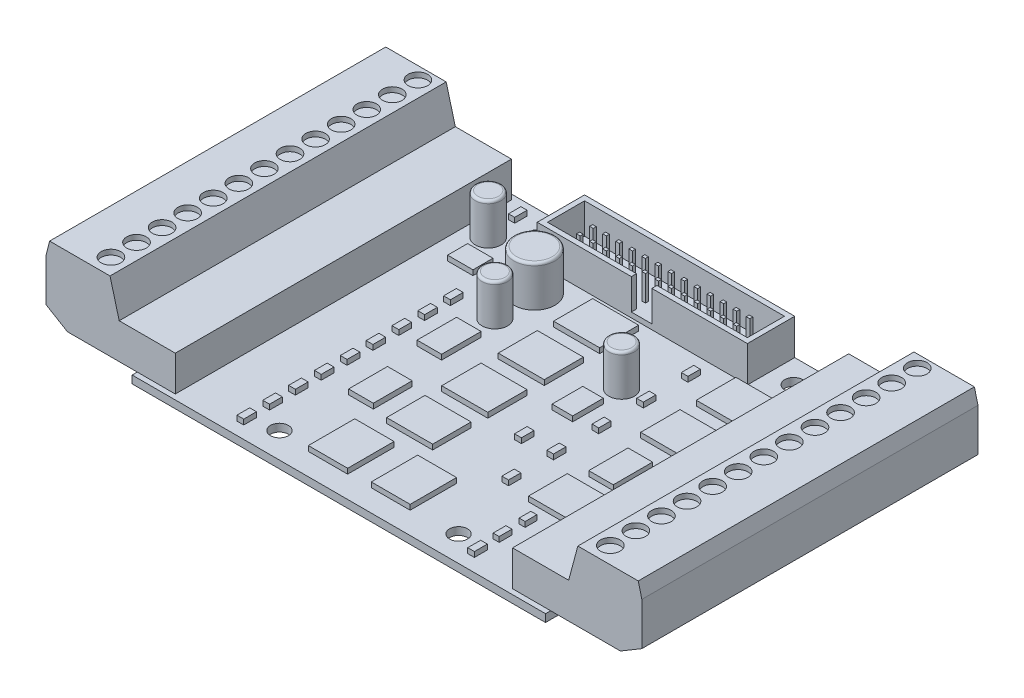
SolidWorks part; units mm, degrees
ref_plane "Front Plane" through (0, 0, 0) normal (0, 0, 1) x (1, 0, 0)
ref_plane "Top Plane" through (0, 0, 0) normal (0, 1, 0) x (1, 0, 0)
ref_plane "Right Plane" through (0, 0, 0) normal (1, 0, 0) x (0, 0, -1)
sketch "Sketch1" plane through (0, 0, 0) normal (0, 1, 0) x (1, 0, 0)
  line L0 (91.1211, 240.7605) -> (689.1211, 240.7605) construction
  line L1 (55.2, -33.85) -> (-55.2, -33.85)
  line L2 (55.2, -33.85) -> (55.2, 33.85)
  line L3 (55.2, 33.85) -> (-55.2, 33.85)
  line L4 (-55.2, -33.85) -> (-55.2, 33.85)
  line L5 (0, 33.85) -> (0, -33.85) construction
  line L6 (55.2, 0) -> (-55.2, 0) construction
  point P0 (0, 0)
  dimension "D1" = 110.4
  dimension "D2" = 67.7
sketch "Sketch3" plane through (0, 0, 0) normal (0, 1, 0) x (1, 0, 0)
  line L1 (-40.4, 33.85) -> (40.4, 33.85)
  line L2 (-40.4, 33.85) -> (-40.4, -33.85)
  line L3 (-40.4, -33.85) -> (40.4, -33.85)
  line L4 (40.4, 33.85) -> (40.4, -33.85)
  line L5 (0, -33.85) -> (0, 33.85) construction
  line L6 (-40.4, 0) -> (40.4, 0) construction
  line L8 (55.2, -33.85) -> (-55.2, -33.85) construction
  line L9 (55.2, 33.85) -> (-55.2, 33.85) construction
  circle A0 centre (-24.1, 29.15) radius 1.75
  circle A1 centre (25.9, 29.15) radius 1.75
  circle A2 centre (-16.6, -28.85) radius 1.75
  circle A3 centre (18.4, -28.85) radius 1.75
  point P4 (-40.4, 37.8234)
  point P5 (-40.4, 33.85)
  point P6 (0, 0)
  point P7 (0, 0)
  point P18 (0, 0)
  point P19 (0, 0)
  point P20 (0, 0)
  point P21 (0, -33.85)
  point P24 (0, 0)
  point P27 (-24.1, 29.2245)
  point P28 (0, 0)
  point P460 (0, 0)
  dimension "D1" = 3.5
  dimension "D2" = 50
  dimension "D3" = 16.3
  dimension "D7" = 5
  dimension "D8" = 35
  dimension "D9" = 23.8
  dimension "D6" = 58
  dimension "D4" = 80.8
  dimension "D5" = 14.5
extrude "Boss-Extrude1" add sketch "Sketch3" against normal blind 1.5
sketch "Sketch4" plane through (0, 0, 0) normal (0, 1, 0) x (1, 0, 0)
  line L0 (55.2, 33.85) -> (-55.2, 33.85) construction
  line L1 (-19.668, 33.85) -> (21.4062, 33.85)
  line L2 (-19.668, 33.85) -> (-19.668, 24.5976)
  line L3 (-19.668, 24.5976) -> (21.4062, 24.5976)
  line L4 (21.4062, 33.85) -> (21.4062, 24.5976)
  line L5 (0.8691, 24.5976) -> (0.8691, 33.85) construction
  line L6 (-19.668, 29.2238) -> (21.4062, 29.2238) construction
  line L7 (-21.0297, 6.4362) -> (-22.3587, 6.4362)
  line L8 (19.9963, 23.7647) -> (29.04, 23.7647)
  line L9 (19.9963, 23.7647) -> (19.9963, 16.0201)
  line L10 (19.9963, 16.0201) -> (29.04, 16.0201)
  line L11 (29.04, 23.7647) -> (29.04, 16.0201)
  line L12 (24.5181, 16.0201) -> (24.5181, 23.7647) construction
  line L13 (19.9963, 19.8924) -> (29.04, 19.8924) construction
  line L14 (13.8505, 21.6661) -> (15.1496, 21.6661)
  line L15 (13.8505, 21.6661) -> (13.8505, 19.2428)
  line L16 (13.8505, 19.2428) -> (15.1496, 19.2428)
  line L17 (15.1496, 21.6661) -> (15.1496, 19.2428)
  line L18 (14.5001, 19.2428) -> (14.5001, 21.6661) construction
  line L19 (13.8505, 20.4545) -> (15.1496, 20.4545) construction
  line L20 (19.9963, 12.8382) -> (29.04, 12.8382)
  line L21 (19.9963, 12.8382) -> (19.9963, 5.1557)
  line L22 (19.9963, 5.1557) -> (29.04, 5.1557)
  line L23 (29.04, 12.8382) -> (29.04, 5.1557)
  line L24 (24.5181, 5.1557) -> (24.5181, 12.8382) construction
  line L25 (19.9963, 8.9969) -> (29.04, 8.9969) construction
  line L26 (13.8505, 12.9602) -> (15.1496, 12.9602)
  line L27 (13.8505, 12.9602) -> (13.8505, 10.5213)
  line L28 (13.8505, 10.5213) -> (15.1496, 10.5213)
  line L29 (15.1496, 12.9602) -> (15.1496, 10.5213)
  line L30 (14.5001, 10.5213) -> (14.5001, 12.9602) construction
  line L31 (13.8505, 11.7407) -> (15.1496, 11.7407) construction
  line L32 (6.5624, 7.2753) -> (10.5826, 7.2753)
  line L33 (6.5624, 7.2753) -> (6.5624, 1.275)
  line L34 (6.5624, 1.275) -> (10.5826, 1.275)
  line L35 (10.5826, 7.2753) -> (10.5826, 1.275)
  line L36 (8.5725, 1.275) -> (8.5725, 7.2753) construction
  line L37 (6.5624, 4.2751) -> (10.5826, 4.2751) construction
  line L38 (13.8505, 4.1551) -> (15.1496, 4.1551)
  line L39 (13.8505, 4.1551) -> (13.8505, 1.795)
  line L40 (13.8505, 1.795) -> (15.1496, 1.795)
  line L41 (15.1496, 4.1551) -> (15.1496, 1.795)
  line L42 (14.5001, 1.795) -> (14.5001, 4.1551) construction
  line L43 (13.8505, 2.9751) -> (15.1496, 2.9751) construction
  line L44 (21.4062, 1.275) -> (26.2051, 1.275)
  line L45 (21.4062, 1.275) -> (21.4062, -6.4055)
  line L46 (21.4062, -6.4055) -> (26.2051, -6.4055)
  line L47 (26.2051, 1.275) -> (26.2051, -6.4055)
  line L48 (23.8056, -6.4055) -> (23.8056, 1.275) construction
  line L49 (21.4062, -2.5653) -> (26.2051, -2.5653) construction
  line L50 (19.8251, -9.0027) -> (28.7983, -9.0027)
  line L51 (19.8251, -9.0027) -> (19.8251, -16.5844)
  line L52 (19.8251, -16.5844) -> (28.7983, -16.5844)
  line L53 (28.7983, -9.0027) -> (28.7983, -16.5844)
  line L54 (24.3117, -16.5844) -> (24.3117, -9.0027) construction
  line L55 (19.8251, -12.7935) -> (28.7983, -12.7935) construction
  line L56 (-7.3293, 23.0883) -> (1.6699, 23.0883)
  line L57 (-7.3293, 23.0883) -> (-7.3293, 15.4512)
  line L58 (-7.3293, 15.4512) -> (1.6699, 15.4512)
  line L59 (1.6699, 23.0883) -> (1.6699, 15.4512)
  line L60 (-2.8297, 15.4512) -> (-2.8297, 23.0883) construction
  line L61 (-7.3293, 19.2698) -> (1.6699, 19.2698) construction
  line L62 (1.6699, 12.2803) -> (-7.3293, 12.2803)
  line L63 (1.6699, 12.2803) -> (1.6699, 4.6416)
  line L64 (1.6699, 4.6416) -> (-7.3293, 4.6416)
  line L65 (-7.3293, 12.2803) -> (-7.3293, 4.6416)
  line L66 (-2.8297, 4.6416) -> (-2.8297, 12.2803) construction
  line L67 (1.6699, 8.461) -> (-7.3293, 8.461) construction
  line L68 (1.6699, 1.275) -> (-7.3293, 1.275)
  line L69 (1.6699, 1.275) -> (1.6699, -6.4055)
  line L70 (1.6699, -6.4055) -> (-7.3293, -6.4055)
  line L71 (-7.3293, 1.275) -> (-7.3293, -6.4055)
  line L72 (-2.8297, -6.4055) -> (-2.8297, 1.275) construction
  line L73 (1.6699, -2.5653) -> (-7.3293, -2.5653) construction
  line L74 (1.6699, -9.6712) -> (-7.3293, -9.6712)
  line L75 (1.6699, -9.6712) -> (1.6699, -17.1794)
  line L76 (1.6699, -17.1794) -> (-7.3293, -17.1794)
  line L77 (-7.3293, -9.6712) -> (-7.3293, -17.1794)
  line L78 (-2.8297, -17.1794) -> (-2.8297, -9.6712) construction
  line L79 (1.6699, -13.4253) -> (-7.3293, -13.4253) construction
  line L80 (7.9189, -4.9721) -> (9.2725, -4.9721)
  line L81 (7.9189, -4.9721) -> (7.9189, -7.4238)
  line L82 (7.9189, -7.4238) -> (9.2725, -7.4238)
  line L83 (9.2725, -4.9721) -> (9.2725, -7.4238)
  line L84 (8.5957, -7.4238) -> (8.5957, -4.9721) construction
  line L85 (7.9189, -6.1979) -> (9.2725, -6.1979) construction
  line L86 (13.8505, -4.6146) -> (15.1496, -4.6146)
  line L87 (13.8505, -4.6146) -> (13.8505, -7.0407)
  line L88 (13.8505, -7.0407) -> (15.1496, -7.0407)
  line L89 (15.1496, -4.6146) -> (15.1496, -7.0407)
  line L90 (14.5001, -7.0407) -> (14.5001, -4.6146) construction
  line L91 (13.8505, -5.8276) -> (15.1496, -5.8276) construction
  line L92 (13.8505, -13.4253) -> (15.1496, -13.4253)
  line L93 (13.8505, -13.4253) -> (13.8505, -15.8259)
  line L94 (13.8505, -15.8259) -> (15.1496, -15.8259)
  line L95 (15.1496, -13.4253) -> (15.1496, -15.8259)
  line L96 (14.5001, -15.8259) -> (14.5001, -13.4253) construction
  line L97 (13.8505, -14.6256) -> (15.1496, -14.6256) construction
  line L98 (22.6282, -18.9476) -> (23.8056, -18.9476)
  line L99 (22.6282, -18.9476) -> (22.6282, -21.2446)
  line L100 (22.6282, -21.2446) -> (23.8056, -21.2446)
  line L101 (23.8056, -18.9476) -> (23.8056, -21.2446)
  line L102 (23.2169, -21.2446) -> (23.2169, -18.9476) construction
  line L103 (22.6282, -20.0961) -> (23.8056, -20.0961) construction
  line L104 (22.6282, -23.8187) -> (23.8056, -23.8187)
  line L105 (22.6282, -23.8187) -> (22.6282, -26.317)
  line L106 (22.6282, -26.317) -> (23.8056, -26.317)
  line L107 (23.8056, -23.8187) -> (23.8056, -26.317)
  line L108 (23.2169, -26.317) -> (23.2169, -23.8187) construction
  line L109 (22.6282, -25.0679) -> (23.8056, -25.0679) construction
  line L110 (22.6282, -28.7483) -> (23.9342, -28.7483)
  line L111 (22.6282, -28.7483) -> (22.6282, -31.2801)
  line L112 (22.6282, -31.2801) -> (23.9342, -31.2801)
  line L113 (23.9342, -28.7483) -> (23.9342, -31.2801)
  line L114 (23.2812, -31.2801) -> (23.2812, -28.7483) construction
  line L115 (22.6282, -30.0142) -> (23.9342, -30.0142) construction
  line L116 (2.0673, -20.4985) -> (9.6601, -20.4985)
  line L117 (2.0673, -20.4985) -> (2.0673, -29.5704)
  line L118 (2.0673, -29.5704) -> (9.6601, -29.5704)
  line L119 (9.6601, -20.4985) -> (9.6601, -29.5704)
  line L120 (5.8637, -29.5704) -> (5.8637, -20.4985) construction
  line L121 (2.0673, -25.0345) -> (9.6601, -25.0345) construction
  line L122 (-10.237, -20.4985) -> (-2.5515, -20.4985)
  line L123 (-10.237, -20.4985) -> (-10.237, -29.5704)
  line L124 (-10.237, -29.5704) -> (-2.5515, -29.5704)
  line L125 (-2.5515, -20.4985) -> (-2.5515, -29.5704)
  line L126 (-6.3943, -29.5704) -> (-6.3943, -20.4985) construction
  line L127 (-10.237, -25.0345) -> (-2.5515, -25.0345) construction
  line L128 (-15.8868, -8.4499) -> (-11.0554, -8.4499)
  line L129 (-15.8868, -8.4499) -> (-15.8868, -16.0475)
  line L130 (-15.8868, -16.0475) -> (-11.0554, -16.0475)
  line L131 (-11.0554, -8.4499) -> (-11.0554, -16.0475)
  line L132 (-13.4711, -16.0475) -> (-13.4711, -8.4499) construction
  line L133 (-15.8868, -12.2487) -> (-11.0554, -12.2487) construction
  line L134 (-17.4644, 6.6335) -> (-12.6701, 6.6335)
  line L135 (-17.4644, 6.6335) -> (-17.4644, -1.0907)
  line L136 (-17.4644, -1.0907) -> (-12.6701, -1.0907)
  line L137 (-12.6701, 6.6335) -> (-12.6701, -1.0907)
  line L138 (-15.0673, -1.0907) -> (-15.0673, 6.6335) construction
  line L139 (-17.4644, 2.7714) -> (-12.6701, 2.7714) construction
  line L140 (-28.86, 20.1881) -> (-23.9, 20.1881)
  line L141 (-28.86, 20.1881) -> (-28.86, 16.2723)
  line L142 (-28.86, 16.2723) -> (-23.9, 16.2723)
  line L143 (-23.9, 20.1881) -> (-23.9, 16.2723)
  line L144 (-26.38, 16.2723) -> (-26.38, 20.1881) construction
  line L145 (-28.86, 18.2302) -> (-23.9, 18.2302) construction
  line L146 (-29.9052, 31.6469) -> (-28.6965, 31.6469)
  line L147 (-29.9052, 31.6469) -> (-29.9052, 29.2238)
  line L148 (-29.9052, 29.2238) -> (-28.6965, 29.2238)
  line L149 (-28.6965, 31.6469) -> (-28.6965, 29.2238)
  line L150 (-29.3008, 29.2238) -> (-29.3008, 31.6469) construction
  line L151 (-29.9052, 30.4353) -> (-28.6965, 30.4353) construction
  line L152 (-21.0297, 11.4862) -> (-22.3587, 11.4862)
  line L153 (-21.0297, 11.4862) -> (-21.0297, 8.9969)
  line L154 (-21.0297, 8.9969) -> (-22.3587, 8.9969)
  line L155 (-22.3587, 11.4862) -> (-22.3587, 8.9969)
  line L156 (-21.6942, 8.9969) -> (-21.6942, 11.4862) construction
  line L157 (-21.0297, 10.2416) -> (-22.3587, 10.2416) construction
  line L158 (-21.0297, 6.4362) -> (-21.0297, 3.9469)
  line L159 (-21.0297, 3.9469) -> (-22.3587, 3.9469)
  line L160 (-22.3587, 6.4362) -> (-22.3587, 3.9469)
  line L161 (-21.0297, 1.3862) -> (-22.3587, 1.3862)
  line L162 (-21.0297, 1.3862) -> (-21.0297, -1.1031)
  line L163 (-21.0297, -1.1031) -> (-22.3587, -1.1031)
  line L164 (-22.3587, 1.3862) -> (-22.3587, -1.1031)
  line L165 (-21.0297, -3.6638) -> (-22.3587, -3.6638)
  line L166 (-21.0297, -3.6638) -> (-21.0297, -6.1531)
  line L167 (-21.0297, -6.1531) -> (-22.3587, -6.1531)
  line L168 (-22.3587, -3.6638) -> (-22.3587, -6.1531)
  line L169 (-21.0297, -8.7138) -> (-22.3587, -8.7138)
  line L170 (-21.0297, -8.7138) -> (-21.0297, -11.2031)
  line L171 (-21.0297, -11.2031) -> (-22.3587, -11.2031)
  line L172 (-22.3587, -8.7138) -> (-22.3587, -11.2031)
  line L173 (-21.0297, -13.7638) -> (-22.3587, -13.7638)
  line L174 (-21.0297, -13.7638) -> (-21.0297, -16.2531)
  line L175 (-21.0297, -16.2531) -> (-22.3587, -16.2531)
  line L176 (-22.3587, -13.7638) -> (-22.3587, -16.2531)
  line L177 (-21.0297, -18.8138) -> (-22.3587, -18.8138)
  line L178 (-21.0297, -18.8138) -> (-21.0297, -21.3031)
  line L179 (-21.0297, -21.3031) -> (-22.3587, -21.3031)
  line L180 (-22.3587, -18.8138) -> (-22.3587, -21.3031)
  line L181 (-21.0297, -23.8638) -> (-22.3587, -23.8638)
  line L182 (-21.0297, -23.8638) -> (-21.0297, -26.3531)
  line L183 (-21.0297, -26.3531) -> (-22.3587, -26.3531)
  line L184 (-22.3587, -23.8638) -> (-22.3587, -26.3531)
  line L185 (-21.0297, -28.9138) -> (-22.3587, -28.9138)
  line L186 (-21.0297, -28.9138) -> (-21.0297, -31.4031)
  line L187 (-21.0297, -31.4031) -> (-22.3587, -31.4031)
  line L188 (-22.3587, -28.9138) -> (-22.3587, -31.4031)
  circle A0 centre (-28.8605, 24.211) radius 2.5197
  circle A1 centre (-14.8844, 19.2663) radius 4.0045
  circle A2 centre (-14.5083, 11.1576) radius 2.5004
  circle A3 centre (9.7767, 11.6448) radius 2.5023
  point P122 (14.5001, 2.9751)
  point P126 (14.5001, 11.7407)
  point P130 (14.5001, 20.4545)
  point P156 (24.5181, 19.8924)
  point P172 (-2.8297, 19.2698)
  point P178 (24.5181, 8.9969)
  point P187 (23.8056, -2.5653)
  point P192 (8.5725, 4.2751)
  point P198 (-2.8297, -13.4253)
  point P204 (-2.8297, -2.5653)
  point P212 (14.5001, -5.8276)
  point P217 (23.2169, -25.0679)
  point P226 (8.5957, -6.1979)
  point P232 (14.5001, -14.6256)
  point P254 (-26.38, 18.2302)
  point P269 (23.2169, -20.0961)
  point P271 (23.2812, -30.0142)
  point P290 (-6.3943, -25.0345)
  point P299 (24.3117, -12.7935)
  point P312 (-15.0673, 2.7714)
  point P327 (5.8637, -25.0345)
  point P333 (-13.4711, -12.2487)
  point P336 (-29.3008, 30.4353)
  point P341 (-2.8297, 8.461)
  point P360 (-21.6942, 10.2416)
  point P408 (0.8691, 29.2238)
  dimension "D1" = 9
extrude "Boss-Extrude2" add sketch "Sketch4" along normal blind 1
sketch "Sketch5" plane through (0, 0, 33.85) normal (0, 0, 1) x (1, 0, 0)
  line L0 (-43.3141, 0) -> (-43.3141, 2.4964)
  line L1 (-43.3141, 2.4964) -> (-58.2287, 2.4964)
  line L2 (-58.2287, 2.4964) -> (-54.0372, 0)
  line L3 (-54.0372, 0) -> (-43.3141, 0)
  line L4 (-45.7175, 13.6096) -> (-57.5243, 13.6096)
  line L5 (-57.5243, 13.6096) -> (-58.2287, 10.8389)
  line L6 (-58.2287, 10.8389) -> (-58.2287, 2.4964)
  line L7 (-58.2287, 2.4964) -> (-43.3141, 2.4964)
  line L8 (-43.3141, 2.4964) -> (-43.9236, 6.9197)
  line L9 (-43.9236, 6.9197) -> (-45.7175, 13.6096)
  line L10 (-43.9236, 6.9197) -> (-32.9585, 6.9197)
  line L11 (-32.9585, 6.9197) -> (-32.9585, 0)
  line L12 (55.2, 0) -> (-55.2, 0) construction
  line L13 (-32.9585, 0) -> (-43.3141, 0)
  line L14 (0, 0) -> (0, 9.0322) construction
  line L15 (32.9585, 0) -> (43.3141, 0)
  line L16 (32.9585, 6.9197) -> (32.9585, 0)
  line L17 (43.9236, 6.9197) -> (32.9585, 6.9197)
  line L18 (43.9236, 6.9197) -> (45.7175, 13.6096)
  line L19 (43.3141, 2.4964) -> (43.9236, 6.9197)
  line L20 (58.2287, 2.4964) -> (43.3141, 2.4964)
  line L21 (58.2287, 10.8389) -> (58.2287, 2.4964)
  line L22 (57.5243, 13.6096) -> (58.2287, 10.8389)
  line L23 (45.7175, 13.6096) -> (57.5243, 13.6096)
  line L24 (54.0372, 0) -> (43.3141, 0)
  line L25 (58.2287, 2.4964) -> (54.0372, 0)
  line L26 (43.3141, 2.4964) -> (58.2287, 2.4964)
  line L27 (43.3141, 0) -> (43.3141, 2.4964)
  line L28 (55.2, 0) -> (-55.2, 0) construction
  point P1 (-47.0017, 0)
  point P10 (0, 0)
  point P29 (-46.0674, 11.883)
  point P30 (-45.0209, 9.051)
  point P31 (0, 0)
  point P34 (-43.3141, 2.4964)
  point P35 (0, 0)
  point P36 (-54.0372, 0)
  point P37 (-45.7175, 13.6096)
  point P38 (-43.9236, 6.9197)
  line M13 (40.4, 0) -> (-40.4, 0)
  line M14 (-40.4, 0) -> (-40.4, -1.5)
  line M16 (40.4, -1.5) -> (40.4, 0)
extrude "Boss-Extrude3" add sketch "Sketch5" against normal offset from surface (65.7 mm away) 1 from offset 1 contours L8 L9 L4 L5 L6 L1 | L2 L3 L0 L1 | L13 L11 L10 L8 L0 M14 M13 | L23 L18 L19 L20 L21 L22 | L27 L24 L25 L20 | L15 L27 L19 L17 L16 M13 M16 region at (-49.7807, 1.3162, 33.85) region at (38.2357, 3.4965, 33.85) region at (-38.2357, 3.4965, 33.85) region at (-51.2239, 7.8575, 33.85) region at (49.7807, 1.3162, 33.85) region at (51.2239, 7.8575, 33.85) up to face at (0.4346, -0.125, -33.85) offset against normal yes
sketch "Sketch6" plane through (0, 1, 0) normal (0, 1, 0) x (1, 0, 0)
  line L0 (16.4443, 30.032) -> (16.4443, 30.6224)
  line L1 (15.7415, 30.032) -> (16.4443, 30.032)
  line L2 (15.7415, 30.6224) -> (15.7415, 30.032)
  line L3 (16.4443, 30.6224) -> (15.7415, 30.6224)
  line L4 (-11.6057, 30.032) -> (-11.6057, 30.6224)
  line L5 (-12.3085, 30.032) -> (-11.6057, 30.032)
  line L6 (-12.3085, 30.6224) -> (-12.3085, 30.032)
  line L7 (-11.6057, 30.6224) -> (-12.3085, 30.6224)
  line L8 (-9.0557, 30.032) -> (-9.0557, 30.6224)
  line L9 (-9.7585, 30.032) -> (-9.0557, 30.032)
  line L10 (-9.7585, 30.6224) -> (-9.7585, 30.032)
  line L11 (-9.0557, 30.6224) -> (-9.7585, 30.6224)
  line L12 (-6.5057, 30.032) -> (-6.5057, 30.6224)
  line L13 (-7.2085, 30.032) -> (-6.5057, 30.032)
  line L14 (-7.2085, 30.6224) -> (-7.2085, 30.032)
  line L15 (-6.5057, 30.6224) -> (-7.2085, 30.6224)
  line L16 (-3.9557, 30.032) -> (-3.9557, 30.6224)
  line L17 (-4.6585, 30.032) -> (-3.9557, 30.032)
  line L18 (-4.6585, 30.6224) -> (-4.6585, 30.032)
  line L19 (-3.9557, 30.6224) -> (-4.6585, 30.6224)
  line L20 (-1.4057, 30.032) -> (-1.4057, 30.6224)
  line L21 (-2.1085, 30.032) -> (-1.4057, 30.032)
  line L22 (-2.1085, 30.6224) -> (-2.1085, 30.032)
  line L23 (-1.4057, 30.6224) -> (-2.1085, 30.6224)
  line L24 (1.1443, 30.032) -> (1.1443, 30.6224)
  line L25 (0.4415, 30.032) -> (1.1443, 30.032)
  line L26 (0.4415, 30.6224) -> (0.4415, 30.032)
  line L27 (1.1443, 30.6224) -> (0.4415, 30.6224)
  line L28 (3.6943, 30.032) -> (3.6943, 30.6224)
  line L29 (2.9915, 30.032) -> (3.6943, 30.032)
  line L30 (2.9915, 30.6224) -> (2.9915, 30.032)
  line L31 (3.6943, 30.6224) -> (2.9915, 30.6224)
  line L32 (6.2443, 30.032) -> (6.2443, 30.6224)
  line L33 (5.5415, 30.032) -> (6.2443, 30.032)
  line L34 (5.5415, 30.6224) -> (5.5415, 30.032)
  line L35 (6.2443, 30.6224) -> (5.5415, 30.6224)
  line L36 (8.7943, 30.032) -> (8.7943, 30.6224)
  line L37 (8.0915, 30.032) -> (8.7943, 30.032)
  line L38 (8.0915, 30.6224) -> (8.0915, 30.032)
  line L39 (8.7943, 30.6224) -> (8.0915, 30.6224)
  line L40 (11.3443, 30.032) -> (11.3443, 30.6224)
  line L41 (10.6415, 30.032) -> (11.3443, 30.032)
  line L42 (10.6415, 30.6224) -> (10.6415, 30.032)
  line L43 (11.3443, 30.6224) -> (10.6415, 30.6224)
  line L44 (13.8943, 30.032) -> (13.8943, 30.6224)
  line L45 (13.1915, 30.032) -> (13.8943, 30.032)
  line L46 (13.1915, 30.6224) -> (13.1915, 30.032)
  line L47 (13.8943, 30.6224) -> (13.1915, 30.6224)
  line L48 (-14.1557, 27.482) -> (-14.1557, 28.0724)
  line L49 (-14.8585, 27.482) -> (-14.1557, 27.482)
  line L50 (-14.8585, 28.0724) -> (-14.8585, 27.482)
  line L51 (-14.1557, 28.0724) -> (-14.8585, 28.0724)
  line L52 (-11.6057, 27.482) -> (-11.6057, 28.0724)
  line L53 (-12.3085, 27.482) -> (-11.6057, 27.482)
  line L54 (-12.3085, 28.0724) -> (-12.3085, 27.482)
  line L55 (-11.6057, 28.0724) -> (-12.3085, 28.0724)
  line L56 (-9.0557, 27.482) -> (-9.0557, 28.0724)
  line L57 (-9.7585, 27.482) -> (-9.0557, 27.482)
  line L58 (-9.7585, 28.0724) -> (-9.7585, 27.482)
  line L59 (-9.0557, 28.0724) -> (-9.7585, 28.0724)
  line L60 (-6.5057, 27.482) -> (-6.5057, 28.0724)
  line L61 (-7.2085, 27.482) -> (-6.5057, 27.482)
  line L62 (-7.2085, 28.0724) -> (-7.2085, 27.482)
  line L63 (-6.5057, 28.0724) -> (-7.2085, 28.0724)
  line L64 (-3.9557, 27.482) -> (-3.9557, 28.0724)
  line L65 (-4.6585, 27.482) -> (-3.9557, 27.482)
  line L66 (-4.6585, 28.0724) -> (-4.6585, 27.482)
  line L67 (-3.9557, 28.0724) -> (-4.6585, 28.0724)
  line L68 (-1.4057, 27.482) -> (-1.4057, 28.0724)
  line L69 (-2.1085, 27.482) -> (-1.4057, 27.482)
  line L70 (-2.1085, 28.0724) -> (-2.1085, 27.482)
  line L71 (-1.4057, 28.0724) -> (-2.1085, 28.0724)
  line L72 (1.1443, 27.482) -> (1.1443, 28.0724)
  line L73 (0.4415, 27.482) -> (1.1443, 27.482)
  line L74 (0.4415, 28.0724) -> (0.4415, 27.482)
  line L75 (1.1443, 28.0724) -> (0.4415, 28.0724)
  line L76 (3.6943, 27.482) -> (3.6943, 28.0724)
  line L77 (2.9915, 27.482) -> (3.6943, 27.482)
  line L78 (2.9915, 28.0724) -> (2.9915, 27.482)
  line L79 (3.6943, 28.0724) -> (2.9915, 28.0724)
  line L80 (6.2443, 27.482) -> (6.2443, 28.0724)
  line L81 (5.5415, 27.482) -> (6.2443, 27.482)
  line L82 (5.5415, 28.0724) -> (5.5415, 27.482)
  line L83 (6.2443, 28.0724) -> (5.5415, 28.0724)
  line L84 (8.7943, 27.482) -> (8.7943, 28.0724)
  line L85 (8.0915, 27.482) -> (8.7943, 27.482)
  line L86 (8.0915, 28.0724) -> (8.0915, 27.482)
  line L87 (8.7943, 28.0724) -> (8.0915, 28.0724)
  line L88 (11.3443, 27.482) -> (11.3443, 28.0724)
  line L89 (10.6415, 27.482) -> (11.3443, 27.482)
  line L90 (10.6415, 28.0724) -> (10.6415, 27.482)
  line L91 (11.3443, 28.0724) -> (10.6415, 28.0724)
  line L92 (13.8943, 27.482) -> (13.8943, 28.0724)
  line L93 (13.1915, 27.482) -> (13.8943, 27.482)
  line L94 (13.1915, 28.0724) -> (13.1915, 27.482)
  line L95 (13.8943, 28.0724) -> (13.1915, 28.0724)
  line L96 (-14.1557, 30.032) -> (-14.1557, 30.6224)
  line L97 (-14.8585, 30.032) -> (-14.1557, 30.032)
  line L98 (-14.8585, 30.6224) -> (-14.8585, 30.032)
  line L99 (-14.1557, 30.6224) -> (-14.8585, 30.6224)
  line L100 (15.7415, 27.482) -> (16.4443, 27.482)
  line L101 (15.7415, 28.0724) -> (15.7415, 27.482)
  line L102 (16.4443, 28.0724) -> (15.7415, 28.0724)
  line L103 (16.4443, 27.482) -> (16.4443, 28.0724)
  line L104 (2.7337, 24.5976) -> (2.7337, 25.5976)
  line L105 (2.7337, 25.5976) -> (20.4062, 25.5976)
  line L106 (20.4062, 25.5976) -> (20.4062, 32.85)
  line L107 (20.4062, 32.85) -> (-18.668, 32.85)
  line L108 (-18.668, 32.85) -> (-18.668, 25.5976)
  line L109 (-18.668, 25.5976) -> (-1.2663, 25.5976)
  line L110 (-1.2663, 25.5976) -> (-1.2663, 24.5976)
  line L111 (-1.2663, 24.5976) -> (2.7337, 24.5976)
  line L112 (-19.668, 33.85) -> (-19.668, 24.5976) construction
  line L113 (55.2, 33.85) -> (-55.2, 33.85) construction
  line L114 (-19.668, 24.5976) -> (21.4062, 24.5976) construction
  line L115 (21.4062, 24.5976) -> (21.4062, 33.85) construction
  line L117 (-19.668, 33.85) -> (21.4062, 33.85)
  line L118 (-19.668, 33.85) -> (-19.668, 24.5976)
  line L119 (-19.668, 24.5976) -> (21.4062, 24.5976)
  line L120 (21.4062, 33.85) -> (21.4062, 24.5976)
  line L121 (0.8691, 24.5976) -> (0.8691, 33.85) construction
  line L122 (-19.668, 29.2238) -> (21.4062, 29.2238) construction
  point P301 (0.8691, 29.2238)
  line M13 (-19.668, 33.85) -> (-19.668, 24.5976)
  line M14 (-19.668, 24.5976) -> (21.4062, 24.5976)
  line M15 (21.4062, 24.5976) -> (21.4062, 33.85)
  line M16 (21.4062, 33.85) -> (-19.668, 33.85)
  dimension "D1" = 1
  dimension "D2" = 1
  dimension "D3" = 1
  dimension "D4" = 1
extrude "Boss-Extrude4" add sketch "Sketch6" along normal blind 6 contours L110 L109 L108 L107 L106 L105 L104 M14 M15 M16 M13 region at (3.1547, 1, -25.0976)
extrude "Boss-Extrude5" add sketch "Sketch6<3>" along normal blind 5 contours L96 L99 L98 L97 | L4 L7 L6 L5 | L8 L11 L10 L9 | L12 L15 L14 L13 | L48 L51 L50 L49 | L52 L55 L54 L53 | L56 L59 L58 L57 | L60 L63 L62 L61 | L16 L19 L18 L17 | L64 L67 L66 L65 | L20 L23 L22 L21 | L68 L71 L70 L69 | L24 L27 L26 L25 | L72 L75 L74 L73 | L28 L31 L30 L29 | L76 L79 L78 L77 | L32 L35 L34 L33 | L80 L83 L82 L81 | L36 L39 L38 L37 | L84 L87 L86 L85 | L40 L43 L42 L41 | L88 L91 L90 L89 | L44 L47 L46 L45 | L92 L95 L94 L93 | L0 L3 L2 L1 | L100 L103 L102 L101 region at (16.0929, 1, -30.3272) region at (-11.9571, 1, -30.3272) region at (-9.4071, 1, -30.3272) region at (-6.8571, 1, -30.3272) region at (-4.3071, 1, -30.3272) region at (-1.7571, 1, -30.3272) region at (0.7929, 1, -30.3272) region at (3.3429, 1, -30.3272) region at (5.8929, 1, -30.3272) region at (8.4429, 1, -30.3272) region at (10.9929, 1, -30.3272) region at (13.5429, 1, -30.3272) region at (-14.5071, 1, -27.7772) region at (-11.9571, 1, -27.7772) region at (-9.4071, 1, -27.7772) region at (-6.8571, 1, -27.7772) region at (-4.3071, 1, -27.7772) region at (-1.7571, 1, -27.7772) region at (0.7929, 1, -27.7772) region at (3.3429, 1, -27.7772) region at (5.8929, 1, -27.7772) region at (8.4429, 1, -27.7772) region at (10.9929, 1, -27.7772) region at (13.5429, 1, -27.7772) region at (-14.5071, 1, -30.3272) region at (16.0929, 1, -27.7772)
sketch "Sketch6<3>" plane through (0, 1, 0) normal (0, 1, 0) x (1, 0, 0) same geometry as "Sketch6"
sketch "Sketch8" plane through (0, 1, 0) normal (0, 1, 0) x (1, 0, 0)
  circle A0 centre (9.7767, 11.6448) radius 2.5023 construction
  circle A1 centre (-14.5083, 11.1576) radius 2.5004 construction
  circle A2 centre (-14.8844, 19.2663) radius 4.0045 construction
  circle A3 centre (-28.8605, 24.211) radius 2.5197 construction
  circle A4 centre (9.7767, 11.6448) radius 2.5023
  circle A5 centre (-14.5083, 11.1576) radius 2.5004
  circle A6 centre (-14.8844, 19.2663) radius 4.0045
  circle A7 centre (-28.8605, 24.211) radius 2.5197
extrude "Boss-Extrude6" add sketch "Sketch8" along normal blind 7
fillet "Fillet1" radius 0.5 4 edges at (9.7767, 8, -9.1425) (-14.5083, 8, -8.6572) (-14.8844, 8, -15.2617) (-28.8605, 8, -21.6913)
sketch "Sketch9" plane through (0, 13.6096, 0) normal (0, 1, 0) x (1, 0, 0)
  line L0 (0, 33.85) -> (0, -33.85) construction
  line L1 (0, 33.85) -> (0, -33.85) construction
  circle A0 centre (-48.8002, 30.4123) radius 1.9124
  circle A1 centre (-48.8002, 25.4123) radius 1.9124
  circle A2 centre (-48.8002, 20.4123) radius 1.9124
  circle A3 centre (-48.8002, 15.4123) radius 1.9124
  circle A4 centre (-48.8002, 10.4123) radius 1.9124
  circle A5 centre (-48.8002, 5.4123) radius 1.9124
  circle A6 centre (-48.8002, 0.4123) radius 1.9124
  circle A7 centre (-48.8002, -4.5877) radius 1.9124
  circle A8 centre (-48.8002, -9.5877) radius 1.9124
  circle A9 centre (-48.8002, -14.5877) radius 1.9124
  circle A10 centre (-48.8002, -19.5877) radius 1.9124
  circle A11 centre (-48.8002, -24.5877) radius 1.9124
  circle A12 centre (-48.8002, -29.5877) radius 1.9124
  circle A13 centre (48.8002, -29.5877) radius 1.9124
  circle A14 centre (48.8002, -24.5877) radius 1.9124
  circle A15 centre (48.8002, -19.5877) radius 1.9124
  circle A16 centre (48.8002, -14.5877) radius 1.9124
  circle A17 centre (48.8002, -9.5877) radius 1.9124
  circle A18 centre (48.8002, -4.5877) radius 1.9124
  circle A19 centre (48.8002, 0.4123) radius 1.9124
  circle A20 centre (48.8002, 5.4123) radius 1.9124
  circle A21 centre (48.8002, 10.4123) radius 1.9124
  circle A22 centre (48.8002, 15.4123) radius 1.9124
  circle A23 centre (48.8002, 20.4123) radius 1.9124
  circle A24 centre (48.8002, 25.4123) radius 1.9124
  circle A25 centre (48.8002, 30.4123) radius 1.9124
  dimension "D1" = 13
extrude "Cut-Extrude1" cut sketch "Sketch9" against normal blind 1
